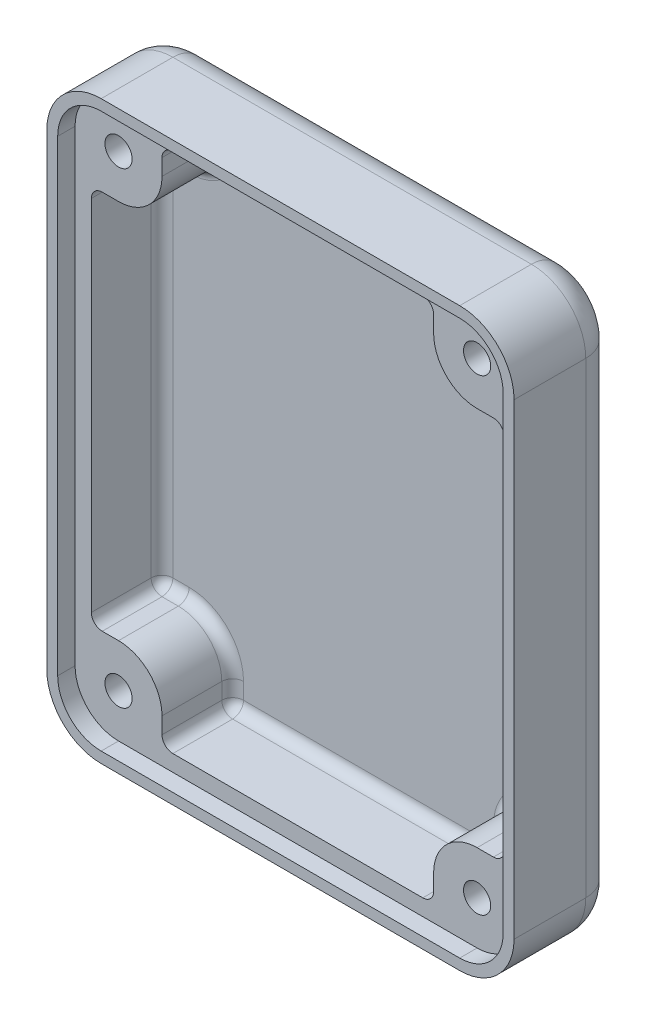
SolidWorks part; units mm, degrees
ref_plane "Front Plane" through (0, 0, 0) normal (0, 0, 1) x (1, 0, 0)
ref_plane "Top Plane" through (0, 0, 0) normal (0, 1, 0) x (1, 0, 0)
ref_plane "Right Plane" through (0, 0, 0) normal (1, 0, 0) x (0, 0, -1)
sketch "Sketch2" plane through (0, 0, 0) normal (0, 0, 1) x (1, 0, 0)
  line L1 (-16.5, 26.5) -> (16.5, 26.5)
  line L2 (-21.5, 21.5) -> (-21.5, -21.5)
  line L3 (-16.5, -26.5) -> (16.5, -26.5)
  line L4 (21.5, 21.5) -> (21.5, -21.5)
  line L5 (-21.5, 26.5) -> (21.5, -26.5) construction
  line L6 (-21.5, -26.5) -> (21.5, 26.5) construction
  arc A0 (-16.5, 26.5) -> (-21.5, 21.5) centre (-16.5, 21.5) ccw
  arc A1 (21.5, 21.5) -> (16.5, 26.5) centre (16.5, 21.5) ccw
  arc A2 (-21.5, -21.5) -> (-16.5, -26.5) centre (-16.5, -21.5) ccw
  arc A3 (16.5, -26.5) -> (21.5, -21.5) centre (16.5, -21.5) ccw
  point P0 (0, 0)
  dimension "D1" = 53
  dimension "D3" = 5
  dimension "D4" = 5
  dimension "D5" = 5
  dimension "D6" = 5
  dimension "D2" = 43
extrude "Boss-Extrude1" add sketch "Sketch2" along normal blind 9.6
sketch "Sketch3" plane through (0, 0, 0) normal (0, 0, 1) x (1, 0, 0)
  line L1 (-16.5, -25.5) -> (16.5, -25.5)
  line L2 (-20.5, -21.5) -> (-20.5, 21.5)
  line L3 (-16.5, 25.5) -> (16.5, 25.5)
  line L4 (20.5, -21.5) -> (20.5, 21.5)
  line L5 (-20.5, -25.5) -> (20.5, 25.5) construction
  line L6 (-20.5, 25.5) -> (20.5, -25.5) construction
  arc A0 (-16.5, 25.5) -> (-20.5, 21.5) centre (-16.5, 21.5) ccw
  arc A1 (20.5, 21.5) -> (16.5, 25.5) centre (16.5, 21.5) ccw
  arc A2 (-20.5, -21.5) -> (-16.5, -25.5) centre (-16.5, -21.5) ccw
  arc A3 (16.5, -25.5) -> (20.5, -21.5) centre (16.5, -21.5) ccw
  point P0 (0, 0)
  dimension "D1" = 51
  dimension "D3" = 4
  dimension "D4" = 4
  dimension "D5" = 4
  dimension "D6" = 4
  dimension "D2" = 41
extrude "Cut-Extrude1" cut sketch "Sketch3" against normal blind 1.6 from offset 9.6
sketch "Sketch4" plane through (0, 0, 0) normal (0, 0, 1) x (1, 0, 0)
  line L0 (-12.5, -21.5) -> (-12.5, -24)
  line L1 (-12.5, -24) -> (12.5, -24)
  line L3 (-12.5, 24) -> (12.5, 24)
  line L4 (19, -17.5) -> (19, 17.5)
  line L5 (-19, -24) -> (19, 24) construction
  line L6 (-19, 24) -> (19, -24) construction
  line L11 (-16.5, -21.5) -> (16.5, 21.5) construction
  line L12 (-16.5, 21.5) -> (16.5, -21.5) construction
  line L13 (-16.5, -17.5) -> (-19, -17.5)
  line L14 (-19, -17.5) -> (-19, 17.5)
  line L15 (12.5, -21.5) -> (12.5, -24)
  line L16 (16.5, -17.5) -> (19, -17.5)
  line L17 (-16.5, 17.5) -> (-19, 17.5)
  line L18 (-12.5, 21.5) -> (-12.5, 24)
  line L19 (12.5, 21.5) -> (12.5, 24)
  line L20 (16.5, 17.5) -> (19, 17.5)
  arc A0 (-16.5, 17.5) -> (-12.5, 21.5) centre (-16.5, 21.5) ccw
  arc A1 (12.5, 21.5) -> (16.5, 17.5) centre (16.5, 21.5) ccw
  arc A2 (-12.5, -21.5) -> (-16.5, -17.5) centre (-16.5, -21.5) ccw
  arc A3 (16.5, -17.5) -> (12.5, -21.5) centre (16.5, -21.5) ccw
  point P0 (0, 0)
  point P6 (0, 0)
extrude "Cut-Extrude2" cut sketch "Sketch4" against normal blind 8.1 from offset 9.6
sketch "Sketch5" plane through (0, 0, 0) normal (0, 0, 1) x (1, 0, 0)
  line L5 (-16.5, -21.5) -> (16.5, 21.5) construction
  line L6 (-16.5, 21.5) -> (16.5, -21.5) construction
  circle A0 centre (-16.5, 21.5) radius 1.25
  circle A1 centre (16.5, 21.5) radius 1.25
  circle A2 centre (-16.5, -21.5) radius 1.25
  circle A3 centre (16.5, -21.5) radius 1.25
  point P0 (0, 0)
extrude "Cut-Extrude3" cut sketch "Sketch5" against normal blind 8.1 from offset 9.6
fillet "Fillet1" radius 3 8 edges at (-20.0355, -25.0355, 0) (-21.5, 0, 0) (-20.0355, 25.0355, 0) (0, 26.5, 0) (20.0355, 25.0355, 0) (21.5, 0, 0) (20.0355, -25.0355, 0) (0, -26.5, 0)
fillet "Fillet2" radius 1 24 edges at (-17.75, -17.5, 1.5) (-12.5, -22.75, 1.5) (12.5, -22.75, 1.5) (17.75, -17.5, 1.5) (17.75, 17.5, 1.5) (12.5, 22.75, 1.5) (-12.5, 22.75, 1.5) (-17.75, 17.5, 1.5) (-12.5, 24, 4.75) (-19, 17.5, 4.75) (-19, -17.5, 4.75) (-12.5, -24, 4.75) (-13.6716, -18.6716, 1.5) (0, -24, 1.5) (12.5, -24, 4.75) (13.6716, -18.6716, 1.5) (19, -17.5, 4.75) (19, 0, 1.5) (19, 17.5, 4.75) (13.6716, 18.6716, 1.5) (12.5, 24, 4.75) (0, 24, 1.5) (-13.6716, 18.6716, 1.5) (-19, 0, 1.5)
